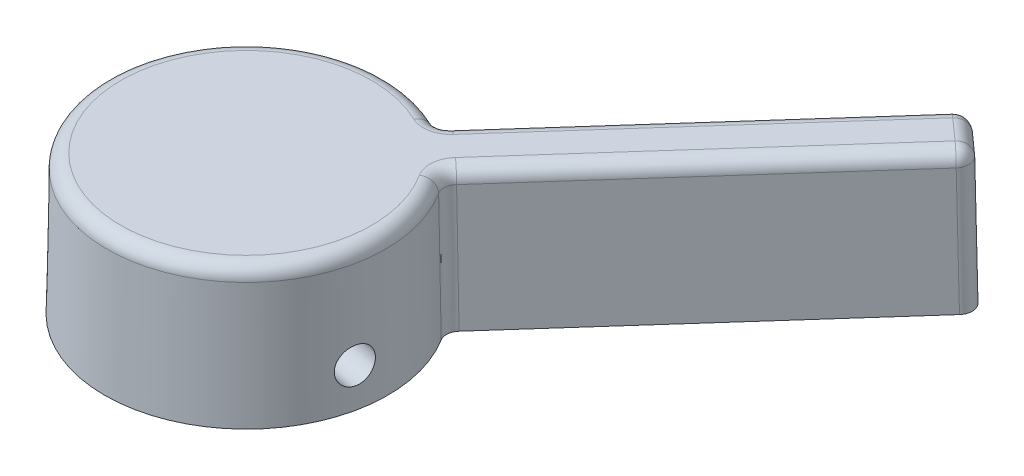
SolidWorks part; units mm, degrees
ref_plane "Plan de face" through (0, 0, 0) normal (0, 0, 1) x (1, 0, 0)
ref_plane "Plan de dessus" through (0, 0, 0) normal (0, 1, 0) x (1, 0, 0)
ref_plane "Plan de droite" through (0, 0, 0) normal (1, 0, 0) x (0, 0, -1)
ref_plane "Plan1" through (0, -53.6046, 0) normal (0, 1, 0) x (-1, 0, 0)
sketch "Esquisse1" plane through (0, -53.6046, 0) normal (0, 1, 0) x (-1, 0, 0)
  line L0 (4.1696, 172.1512) -> (-13.9264, 151.8414)
  line L1 (-13.9264, 151.8414) -> (-10.9399, 149.1805)
  line L2 (-10.9399, 149.1805) -> (7.1561, 169.4902)
  arc A0 (7.1561, 169.4902) -> (4.1696, 172.1512) centre (12.1809, 178.1361) ccw
extrude "Boss.-Extru.1" add sketch "Esquisse1" against normal blind 10 draft 1 draft outward yes
hole_wizard "Perçage1" positions "Esquisse3" profile "Esquisse2" legacy
sketch "Esquisse3" plane through (0, -63.6046, 0) normal (0, -1, 0) x (1, 0, 0)
  point P0 (-12.1809, 178.1361)
sketch "Esquisse2" plane through (-12.1809, -63.6046, 178.1361) normal (1, 0, 0) x (0, 0, -1)
  line L0 (0, 0) -> (0, 6)
  line L1 (0, 6) -> (6.5, 6)
  line L2 (6.5, 6) -> (6.5, 0)
  line L3 (6.5, 0) -> (0, 0)
  line L4 (0, 110) -> (0, -10) construction
  dimension "Diamètre" = 13
  dimension "Profondeur" = 6
ref_plane "Plan2" through (-15.9346, 0, 0.9185) normal (-0.9983, 0, 0.0575) x (0.0575, 0, 0.9983)
fillet "Congé1" radius 0.9916 1 edges tangent propagation no
fillet "Congé2" radius 0.9916 1 edges tangent propagation no
fillet "Congé3" radius 1 8 edges at (14.0496, -58.6046, 151.8343) (12.4331, -53.6046, 150.5109) (10.9328, -58.6046, 149.0572) (5.1373, -53.6046, 161.7057) (2.1508, -53.6046, 159.0447) (-3.8972, -53.6046, 172.1231) (-7.2124, -53.6046, 169.2268) (-18.8334, -53.6046, 185.6024)
sketch "Esquisse6" plane through (0, -63.6046, 0) normal (0, -1, 0) x (1, 0, 0)
  line L0 (-3.4341, 171.588) -> (13.5077, 152.5737) construction
  line L1 (-6.5771, 183.1291) -> (-8.4865, 183.7606)
  line L2 (-13.7031, 185.4857) -> (-15.2046, 184.1478)
  line L3 (-19.3069, 180.4927) -> (-18.8991, 178.5233)
  line L4 (-17.7848, 173.1431) -> (-15.8754, 172.5116)
  line L5 (-10.6588, 170.7865) -> (-9.1572, 172.1244)
  line L6 (-5.0549, 175.7795) -> (-5.4628, 177.7489)
  line L7 (-11.7937, 184.8542) -> (-13.7031, 185.4857)
  line L8 (-9.8244, 185.2621) -> (-11.7937, 184.8542)
  line L9 (-17.174, 183.7399) -> (-17.8054, 181.8305)
  line L10 (-19.5305, 176.6139) -> (-18.1926, 175.1124)
  line L11 (-14.5375, 171.0101) -> (-12.5682, 171.418)
  line L12 (-7.1879, 172.5323) -> (-6.5565, 174.4417)
  line L13 (-4.8314, 179.6583) -> (-6.1692, 181.1598)
  line L14 (-15.2046, 184.1478) -> (-17.174, 183.7399)
  line L15 (-17.8054, 181.8305) -> (-19.3069, 180.4927)
  line L16 (-8.4865, 183.7606) -> (-9.8244, 185.2621)
  line L17 (-6.1692, 181.1598) -> (-6.5771, 183.1291)
  line L18 (-5.4628, 177.7489) -> (-4.8314, 179.6583)
  line L19 (-6.5565, 174.4417) -> (-5.0549, 175.7795)
  line L20 (-9.1572, 172.1244) -> (-7.1879, 172.5323)
  line L21 (-12.5682, 171.418) -> (-10.6588, 170.7865)
  line L22 (-15.8754, 172.5116) -> (-14.5375, 171.0101)
  line L23 (-18.1926, 175.1124) -> (-17.7848, 173.1431)
  line L24 (-18.8991, 178.5233) -> (-19.5305, 176.6139)
  circle A0 centre (-12.1809, 178.1361) radius 6.5 construction
  circle A1 centre (-12.1809, 178.1361) radius 6.5 construction
  dimension "D1" = 13
  dimension "D2" = 13
extrude "Enlèv. mat.-Extru.1" cut sketch "Esquisse6" against normal up to surface (6 mm away) up to face at (-12.1809, -57.6046, 171.6361)
sketch "Esquisse7" plane through (0, -57.6046, 0) normal (0, -1, 0) x (1, 0, 0)
  circle A0 centre (-12.1809, 178.1361) radius 2.3563
extrude "Enlèv. mat.-Extru.2" cut sketch "Esquisse7" against normal blind 0.1
ref_plane "Plan3" through (-35.8773, 0, 173.2284) normal (-0.2028, 0, 0.9792) x (0.9792, 0, 0.2028)
ref_axis "Axe1" through (-12.1809, -63.6046, 178.1361) along (0, 1, 0)
hole_wizard "Trou taraudé M31" positions "Esquisse5" profile "Esquisse4" tap size "M3" standard "ISO"
sketch "Esquisse5" plane through (30.5872, -0.2398, 3.6866) normal (-0.9792, 0, -0.2028) x (-0.2028, 0, 0.9792)
  line L0 (175.7451, -63.3648) -> (177.7562, -63.3648) construction
  line L2 (179.4979, -0.8663) -> (179.4979, 1.3459) construction
  point P0 (179.4979, -60.6046)
  dimension "D1" = 2.7602
sketch "Esquisse4" plane through (-5.816, -60.8443, 179.4543) normal (0, 1, 0) x (-0.2028, 0, 0.9792)
  line L0 (0, 0) -> (0, 9.2511)
  line L1 (0, 9.2511) -> (1.25, 8.5)
  line L2 (1.25, 8.5) -> (1.25, 0)
  line L5 (1.25, 0) -> (0, 0)
  line L10 (0, 9.2511) -> (-1.25, 8.5) construction
  line L11 (0, -6.35) -> (0, 107.95) construction
  dimension "Diamètre du trou pour taraudage" = 2.5
  dimension "Profondeur du trou pour taraudage" = 8.5
  dimension "Angle de pointe" = 118
cosmetic thread "Filetage de perçage3" parameters "D1"=3.6934, "D2"=3
